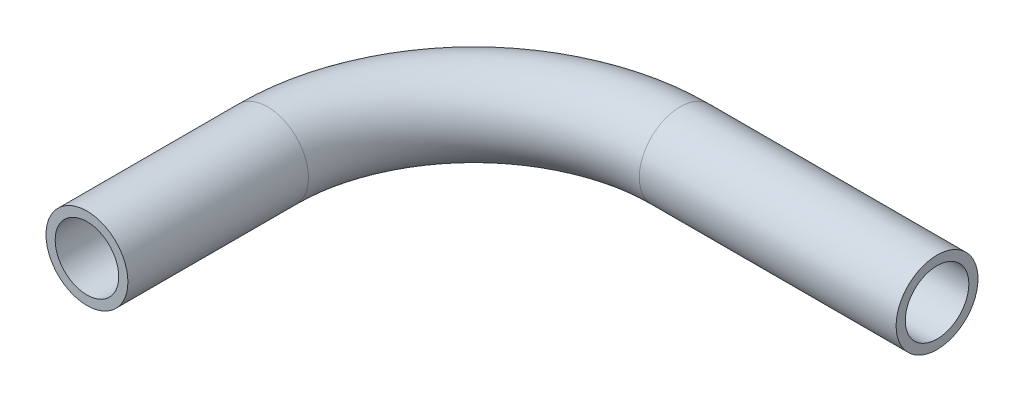
SolidWorks part; units mm, degrees
material "AISI 304"
ref_plane "Front Plane" through (0, 0, 0) normal (0, 0, 1) x (1, 0, 0)
ref_plane "Top Plane" through (0, 0, 0) normal (0, 1, 0) x (1, 0, 0)
ref_plane "Right Plane" through (0, 0, 0) normal (1, 0, 0) x (0, 0, -1)
sketch "Sketch1" plane through (0, 0, 0) normal (0, 1, 0) x (1, 0, 0)
  line L0 (0, 0) -> (0, 14)
  line L1 (16, 30) -> (16.5654, 30)
  line L2 (16.5654, 30) -> (35.9156, 30)
  arc A1 (0, 14) -> (16, 30) centre (16, 14) cw
  point P5 (16.5654, 30)
  point P6 (0, 14)
  point P9 (0, 0)
  point P10 (0, 0)
  dimension "D1" = 35.9156
  dimension "D2" = 16
  dimension "D3" = 14
sketch "Sketch2" plane through (0, 0, 0) normal (0, 0, 1) x (1, 0, 0)
  circle A0 centre (0, 0) radius 3.175
  dimension "D1" = 6.35
sweep "Sweep-Thin1" add profiles "Sketch2" path "Sketch1" parameters "D1"=0.7112
